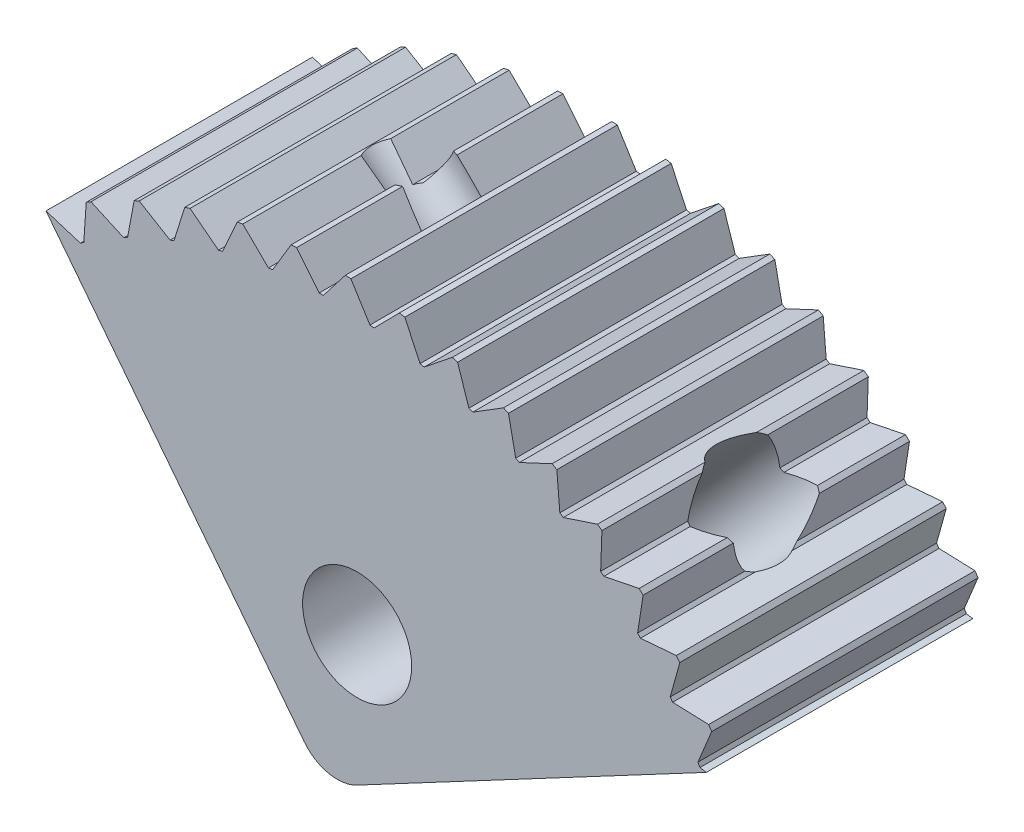
SolidWorks part; units mm, degrees
ref_plane "Front Plane" through (0, 0, 0) normal (0, 0, 1) x (1, 0, 0)
ref_plane "Top Plane" through (0, 0, 0) normal (0, 1, 0) x (1, 0, 0)
ref_plane "Right Plane" through (0, 0, 0) normal (1, 0, 0) x (0, 0, -1)
sketch "Sketch1" plane through (0, 0, 0) normal (0, 0, 1) x (1, 0, 0)
  line L0 (-15.8881, 6.6874) -> (-9.7322, -1.1933)
  line L1 (-8.4748, -1.4607) -> (0.3551, 3.2332)
  line L3 (-16.3589, 19.1239) -> (13.8067, -8.0422) construction
  line L4 (-17.4316, 8.6632) -> (2.569, 4.4101) construction
  line L44 (-9.1521, -1.5558) -> (-7.754, 5.0189) construction
  arc A0 (-15.8881, 6.6874) -> (0.3551, 3.2332) centre (-9.2446, -1.9906) cw
  arc A21 (-8.4748, -1.4607) -> (-9.7322, -1.1933) centre (-8.9441, -0.5777) cw
  circle A22 centre (-8.4713, 1.646) radius 1.3
  point P65 (-9.2952, -2.2794)
  dimension "D3" = 1
  dimension "D6" = 3.2735
  dimension "D2" = 40
  dimension "D4" = 10.929
  dimension "D1" = 100
  dimension "D5" = 70
extrude "Boss-Extrude1" add sketch "Sketch1" along normal blind 3.175 and the other way blind 3.175
sketch "Sketch2" plane through (0, 0, 0) normal (0, 0, 1) x (1, 0, 0)
  line L0 (-8.4748, -1.4607) -> (0.3551, 3.2332) construction
  line L1 (-34.6883, 30.755) -> (-2.4638, 1.7347)
  line L2 (-15.8881, 6.6874) -> (-9.7322, -1.1933) construction
  line L3 (-16.3589, 19.1239) -> (13.8067, -8.0422) construction
  dimension "D1" = 3
ref_plane "Plane1" through (2.1838, 2.425, 0) normal (-0.6692, -0.7431, 0) x (0.7431, -0.6692, 0)
sketch "Sketch4" plane through (-12.9344, -3.8314, 0) normal (-0.4694, 0.883, 0) x (0, 0, 1)
  line L0 (0, -2.9739) -> (0, 11.8581) construction
  line L1 (0, -2.9739) -> (0, 11.8581) construction
  circle A0 centre (0, 11.8581) radius 0.75
  dimension "D1" = 1.5
sweep "Cut-Sweep1" cut profiles "Sketch4" path "Sketch2"
sketch "Sketch3" plane through (2.1838, 2.425, 0) normal (-0.6692, -0.7431, 0) x (0.7431, -0.6692, 0)
  line L2 (-7.8364, -0.625) -> (-3.43, -0.625) construction
  line L4 (-5.6332, 0) -> (-5.6332, -0.625) construction
  circle A0 centre (-5.6332, 0) radius 1.1303
  point P6 (-5.6332, -0.625)
  dimension "D1" = 2.2606
extrude "Cut-Extrude2" cut sketch "Sketch3" along normal blind 6 and the other way blind 10
sketch "Sketch5" plane through (0, 0, 0) normal (0, 0, 1) x (1, 0, 0)
  line L0 (-13.9449, 7.1069) -> (-13.7866, 7.9499)
  line L1 (-14.0335, 7.0606) -> (-13.9449, 7.1069)
  line L2 (-15.8881, 6.6874) -> (-15.0695, 6.4313)
  line L3 (-15.0695, 6.4313) -> (-14.9869, 6.4878)
  line L4 (-14.9869, 6.4878) -> (-14.9293, 7.3436)
  line L5 (-15.8881, 6.6874) -> (-14.9293, 7.3436) construction
  line L6 (-15.4087, 7.0155) -> (-15.0282, 6.4595) construction
  line L7 (-14.3014, 7.6807) -> (-13.9892, 7.0837) construction
  line L8 (-14.8162, 7.4115) -> (-14.0335, 7.0606)
  line L9 (-12.8371, 7.5985) -> (-12.5802, 8.4169)
  line L10 (-12.9305, 7.563) -> (-12.8371, 7.5985)
  line L11 (-13.1232, 8.2105) -> (-12.8838, 7.5808) construction
  line L12 (-13.6663, 8.004) -> (-12.9305, 7.563)
  line L13 (-11.6789, 7.9558) -> (-11.3271, 8.7382)
  line L14 (-11.7759, 7.9316) -> (-11.6789, 7.9558)
  line L15 (-11.8907, 8.5973) -> (-11.7274, 7.9437) construction
  line L16 (-12.4544, 8.4564) -> (-11.7759, 7.9316)
  line L17 (-10.4866, 8.1738) -> (-10.0448, 8.9091)
  line L18 (-10.5858, 8.1612) -> (-10.4866, 8.1738)
  line L19 (-10.6212, 8.8358) -> (-10.5362, 8.1675) construction
  line L20 (-11.1975, 8.7625) -> (-10.5858, 8.1612)
  line L21 (-9.2769, 8.2493) -> (-8.7514, 8.9273)
  line L22 (-9.3769, 8.2485) -> (-9.2769, 8.2493)
  line L23 (-9.3323, 8.9226) -> (-9.3269, 8.2489) construction
  line L24 (-9.9133, 8.9179) -> (-9.3769, 8.2485)
  line L25 (-8.0668, 8.1814) -> (-7.4648, 8.7925)
  line L26 (-8.1661, 8.1924) -> (-8.0668, 8.1814)
  line L27 (-8.0422, 8.8565) -> (-8.1165, 8.1869) construction
  line L28 (-8.6197, 8.9205) -> (-8.1661, 8.1924)
  line L29 (-6.8731, 7.971) -> (-6.2032, 8.5067)
  line L30 (-6.9705, 7.9937) -> (-6.8731, 7.971)
  line L31 (-6.769, 8.6385) -> (-6.9218, 7.9823) construction
  line L32 (-7.3348, 8.7702) -> (-6.9705, 7.9937)
  line L33 (-5.7127, 7.621) -> (-4.9842, 8.0738)
  line L34 (-5.8067, 7.655) -> (-5.7127, 7.621)
  line L35 (-5.5304, 8.2715) -> (-5.7597, 7.638) construction
  line L36 (-6.0767, 8.4692) -> (-5.8067, 7.655)
  line L37 (-4.6018, 7.1364) -> (-3.8248, 7.4999)
  line L38 (-4.6911, 7.1813) -> (-4.6018, 7.1364)
  line L39 (-4.3439, 7.7608) -> (-4.6464, 7.1588) construction
  line L40 (-4.863, 8.0216) -> (-4.6911, 7.1813)
  line L41 (-3.5559, 6.5238) -> (-2.7414, 6.793)
  line L42 (-3.6393, 6.579) -> (-3.5559, 6.5238)
  line L43 (-3.2261, 7.1134) -> (-3.5976, 6.5514) construction
  line L44 (-3.7107, 7.4338) -> (-3.6393, 6.579)
  line L45 (-2.5897, 5.792) -> (-1.7491, 5.9631)
  line L46 (-2.666, 5.8567) -> (-2.5897, 5.792)
  line L47 (-2.1925, 6.3385) -> (-2.6278, 5.8243) construction
  line L48 (-2.6359, 6.7139) -> (-2.666, 5.8567)
  line L49 (-1.7167, 4.9512) -> (-0.8619, 5.0217)
  line L50 (-1.7849, 5.0244) -> (-1.7167, 4.9512)
  line L51 (-1.2578, 5.4469) -> (-1.7508, 4.9878) construction
  line L52 (-1.6537, 5.8721) -> (-1.7849, 5.0244)
  line L53 (-0.9492, 4.0131) -> (-0.092, 3.9822)
  line L54 (-1.0083, 4.0938) -> (-0.9492, 4.0131)
  line L55 (-0.4349, 4.4511) -> (-0.9787, 4.0535) construction
  line L56 (-0.7778, 4.9201) -> (-1.0083, 4.0938)
  line L57 (-0.298, 2.9909) -> (0.5496, 2.8589)
  line L58 (-0.347, 3.078) -> (-0.298, 2.9909)
  line L59 (0.2645, 3.3651) -> (-0.3225, 3.0345) construction
  line L60 (-0.0206, 3.8713) -> (-0.347, 3.078)
  line L61 (0.3551, 3.2332) -> (0.5496, 2.8589)
  line L85 (-0.9262, 5.0979) -> (-1.1391, 4.267) [skipped]
  line L86 (-11.1826, 8.0643) -> (-10.7924, 8.8282) [skipped]
  line L87 (-10.848, 8.8202) -> (-10.2561, 8.1993) [skipped]
  line L88 (-10.2561, 8.1993) -> (-10.1565, 8.2087) [skipped]
  line L89 (-10.1565, 8.2087) -> (-9.6912, 8.9293) [skipped]
  line L90 (-9.7473, 8.9268) -> (-9.2212, 8.2494) [skipped]
  line L91 (-9.2212, 8.2494) -> (-9.1212, 8.2486) [skipped]
  line L92 (-9.1212, 8.2486) -> (-8.5854, 8.9185) [skipped]
  line L93 (-8.6414, 8.9217) -> (-8.1865, 8.1946) [skipped]
  line L94 (-8.1865, 8.1946) -> (-8.0871, 8.1837) [skipped]
  line L95 (-8.0871, 8.1837) -> (-7.4863, 8.796) [skipped]
  line L96 (-7.5417, 8.8049) -> (-7.1626, 8.0355) [skipped]
  line L97 (-7.1626, 8.0355) -> (-7.0648, 8.0147) [skipped]
  line L98 (-7.0648, 8.0147) -> (-6.4053, 8.5631) [skipped]
  line L99 (-6.4595, 8.5776) -> (-6.1601, 7.7738) [skipped]
  line L100 (-6.1601, 7.7738) -> (-6.0648, 7.7432) [skipped]
  line L101 (-6.0648, 7.7432) -> (-5.3533, 8.2222) [skipped]
  line L102 (-5.4058, 8.242) -> (-5.1891, 7.4121) [skipped]
  line L103 (-5.1891, 7.4121) -> (-5.0975, 7.372) [skipped]
  line L104 (-5.0975, 7.372) -> (-4.3411, 7.7766) [skipped]
  line L105 (-4.3914, 7.8017) -> (-4.2597, 6.9541) [skipped]
  line L106 (-4.2597, 6.9541) -> (-4.1725, 6.905) [skipped]
  line L107 (-4.1725, 6.905) -> (-3.3792, 7.2311) [skipped]
  line L108 (-3.4266, 7.2611) -> (-3.3812, 6.4045) [skipped]
  line L109 (-3.3812, 6.4045) -> (-3.2995, 6.3469) [skipped]
  line L110 (-3.2995, 6.3469) -> (-2.4773, 6.5912) [skipped]
  line L111 (-2.5215, 6.6258) -> (-2.5629, 5.769) [skipped]
  line L112 (-2.5629, 5.769) -> (-2.4874, 5.7034) [skipped]
  line L113 (-2.4874, 5.7034) -> (-1.6447, 5.8634) [skipped]
  line L114 (-1.6851, 5.9023) -> (-1.8129, 5.0541) [skipped]
  line L115 (-1.8129, 5.0541) -> (-1.7445, 4.9812) [skipped]
  line L116 (-1.7445, 4.9812) -> (-0.8899, 5.0551) [skipped]
  line L117 (-1.1391, 4.267) -> (-1.0783, 4.1876) [skipped]
  line L118 (-1.0783, 4.1876) -> (-0.2207, 4.1748) [skipped]
  line L119 (-0.2524, 4.221) -> (-0.5482, 3.4159) [skipped]
  line L120 (-0.5482, 3.4159) -> (-0.4958, 3.3307) [skipped]
  line L121 (-0.4958, 3.3307) -> (0.3562, 3.2313) [skipped]
  line L122 (-11.9323, 8.6028) -> (-10.7924, 8.8282) construction
  line L123 (-10.848, 8.8202) -> (-9.6912, 8.9293) construction
  line L124 (-10.2696, 8.8747) -> (-10.2063, 8.204) construction
  line L125 (-9.7473, 8.9268) -> (-8.5854, 8.9185) construction
  line L126 (-9.1663, 8.9227) -> (-9.1712, 8.249) construction
  line L127 (-8.6414, 8.9217) -> (-7.4863, 8.796) construction
  line L128 (-8.0639, 8.8589) -> (-8.1368, 8.1892) construction
  line L129 (-7.5417, 8.8049) -> (-6.4053, 8.5631) construction
  line L130 (-6.9735, 8.684) -> (-7.1137, 8.0251) construction
  line L131 (-6.4595, 8.5776) -> (-5.3533, 8.2222) construction
  line L132 (-5.9064, 8.3999) -> (-6.1125, 7.7585) construction
  line L133 (-5.4058, 8.242) -> (-4.3411, 7.7766) construction
  line L134 (-4.8734, 8.0093) -> (-5.1433, 7.392) construction
  line L135 (-4.3914, 7.8017) -> (-3.3792, 7.2311) construction
  line L136 (-3.8853, 7.5164) -> (-4.2161, 6.9295) construction
  line L137 (-3.4266, 7.2611) -> (-2.4773, 6.5912) construction
  line L138 (-2.952, 6.9261) -> (-3.3404, 6.3757) construction
  line L139 (-2.5215, 6.6258) -> (-1.6447, 5.8634) construction
  line L140 (-2.0831, 6.2446) -> (-2.5251, 5.7362) construction
  line L141 (-1.6851, 5.9023) -> (-0.8899, 5.0551) construction
  line L142 (-1.2875, 5.4787) -> (-1.7787, 5.0176) construction
  line L143 (-0.9262, 5.0979) -> (-0.2207, 4.1748) construction
  line L144 (-0.5734, 4.6364) -> (-1.1087, 4.2273) construction
  line L145 (-0.2524, 4.221) -> (0.3562, 3.2313) construction
  line L146 (0.0519, 3.7262) -> (-0.522, 3.3733) construction
  line L147 (-14.9771, 7.3143) -> (-14.1885, 6.9768) [skipped]
  line L148 (-14.1885, 6.9768) -> (-14.1007, 7.0247) [skipped]
  line L149 (-14.1007, 7.0247) -> (-13.9569, 7.8703) [skipped]
  line L150 (-14.0075, 7.846) -> (-13.257, 7.4305) [skipped]
  line L151 (-13.257, 7.4305) -> (-13.1648, 7.4693) [skipped]
  line L152 (-13.1648, 7.4693) -> (-12.9363, 8.296) [skipped]
  line L153 (-12.989, 8.2769) -> (-12.2844, 7.7878) [skipped]
  line L154 (-12.2844, 7.7878) -> (-12.1888, 7.817) [skipped]
  line L155 (-12.1888, 7.817) -> (-11.8778, 8.6164) [skipped]
  line L156 (-11.9323, 8.6028) -> (-11.2807, 8.0449) [skipped]
  line L157 (-11.2807, 8.0449) -> (-11.1826, 8.0643) [skipped]
  line L158 (-14.9771, 7.3143) -> (-13.9569, 7.8703) construction
  line L159 (-14.467, 7.5923) -> (-14.1446, 7.0008) construction
  line L160 (-14.0075, 7.846) -> (-12.9363, 8.296) construction
  line L161 (-13.4719, 8.071) -> (-13.2109, 7.4499) construction
  line L162 (-12.989, 8.2769) -> (-11.8778, 8.6164) construction
  line L163 (-12.4334, 8.4467) -> (-12.2366, 7.8024) construction
  line L164 (-11.3624, 8.7155) -> (-11.2316, 8.0546) construction
  arc A0 (0.3551, 3.2332) -> (-0.0206, 3.8713) centre (-9.2446, -1.9906) ccw
  arc A1 (0.3551, 3.2332) -> (-15.8881, 6.6874) centre (-9.2446, -1.9906) ccw construction
  arc A3 (-14.9293, 7.3436) -> (-15.8881, 6.6874) centre (-9.2446, -1.9906) ccw
  arc A4 (-13.7866, 7.9499) -> (-14.8162, 7.4115) centre (-9.2446, -1.9906) ccw
  arc A5 (-12.5802, 8.4169) -> (-13.6663, 8.004) centre (-9.2446, -1.9906) ccw
  arc A6 (-11.3271, 8.7382) -> (-12.4544, 8.4564) centre (-9.2446, -1.9906) ccw
  arc A7 (-10.0448, 8.9091) -> (-11.1975, 8.7625) centre (-9.2446, -1.9906) ccw
  arc A8 (-8.7514, 8.9273) -> (-9.9133, 8.9179) centre (-9.2446, -1.9906) ccw
  arc A9 (-7.4648, 8.7925) -> (-8.6197, 8.9205) centre (-9.2446, -1.9906) ccw
  arc A10 (-6.2032, 8.5067) -> (-7.3348, 8.7702) centre (-9.2446, -1.9906) ccw
  arc A11 (-4.9842, 8.0738) -> (-6.0767, 8.4692) centre (-9.2446, -1.9906) ccw
  arc A12 (-3.8248, 7.4999) -> (-4.863, 8.0216) centre (-9.2446, -1.9906) ccw
  arc A13 (-2.7414, 6.793) -> (-3.7107, 7.4338) centre (-9.2446, -1.9906) ccw
  arc A14 (-1.7491, 5.9631) -> (-2.6359, 6.7139) centre (-9.2446, -1.9906) ccw
  arc A15 (-0.8619, 5.0217) -> (-1.6537, 5.8721) centre (-9.2446, -1.9906) ccw
  arc A16 (-0.092, 3.9822) -> (-0.7778, 4.9201) centre (-9.2446, -1.9906) ccw
  point P3 (0.0519, 3.7262)
  point P5 (-0.5734, 4.6364)
  point P6 (-15.0282, 6.4595)
  point P9 (-15.4087, 7.0155)
  point P12 (-1.2875, 5.4787)
  point P13 (-2.0831, 6.2446)
  point P14 (-11.3624, 8.7155)
  point P15 (-12.4334, 8.4467)
  point P16 (-2.952, 6.9261)
  point P17 (-13.4719, 8.071)
  point P19 (-14.467, 7.5923)
  point P24 (-3.8853, 7.5164)
  point P32 (-4.8734, 8.0093)
  point P39 (-5.9064, 8.3999)
  point P40 (-6.9735, 8.684)
  point P46 (-8.0639, 8.8589)
  point P47 (-9.1663, 8.9227)
  point P48 (-10.2696, 8.8747)
  point P91 (-9.0366, -1.0125)
  point P114 (-9.2446, -1.9906)
  point P191 (-9.2446, -1.9906)
  dimension "D2" = 15
  dimension "D1" = 17
  dimension "D4" = 0.6737
  dimension "D5" = 128.243
extrude "Cut-Extrude3" cut sketch "Sketch5" against normal blind 10 and the other way blind 10
